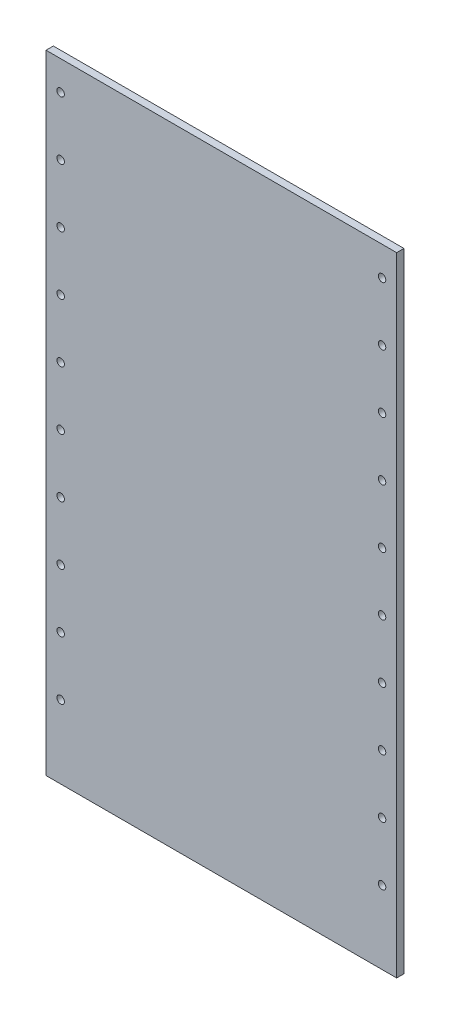
SolidWorks part; units mm, degrees
material "Copper"
ref_plane "Front Plane" through (0, 0, 0) normal (0, 0, 1) x (1, 0, 0)
ref_plane "Top Plane" through (0, 0, 0) normal (0, 1, 0) x (1, 0, 0)
ref_plane "Right Plane" through (0, 0, 0) normal (1, 0, 0) x (0, 0, -1)
sketch "Sketch1" plane through (0, 0, 0) normal (0, 0, 1) x (1, 0, 0)
  line L1 (0, 0) -> (152.4, 0)
  line L2 (0, 0) -> (0, -273.05)
  line L3 (0, -273.05) -> (152.4, -273.05)
  line L4 (152.4, 0) -> (152.4, -273.05)
  circle A0 centre (6.35, -12.7) radius 1.632
  circle A1 centre (146.05, -12.7) radius 1.632
  circle A2 centre (146.05, -38.1) radius 1.632
  circle A3 centre (146.05, -63.5) radius 1.632
  circle A4 centre (146.05, -88.9) radius 1.632
  circle A5 centre (146.05, -114.3) radius 1.632
  circle A6 centre (146.05, -139.7) radius 1.632
  circle A7 centre (146.05, -165.1) radius 1.632
  circle A8 centre (146.05, -190.5) radius 1.632
  circle A9 centre (146.05, -215.9) radius 1.632
  circle A10 centre (146.05, -241.3) radius 1.632
  circle A11 centre (6.35, -38.1) radius 1.6319
  circle A12 centre (6.35, -63.5) radius 1.6319
  circle A13 centre (6.35, -88.9) radius 1.6319
  circle A14 centre (6.35, -114.3) radius 1.6319
  circle A15 centre (6.35, -139.7) radius 1.6319
  circle A16 centre (6.35, -165.1) radius 1.632
  circle A17 centre (6.35, -190.5) radius 1.632
  circle A18 centre (6.35, -215.9) radius 1.632
  circle A19 centre (6.35, -241.3) radius 1.632
  dimension "D3" = 3.2639
  dimension "D1" = 273.05
  dimension "D2" = 152.4
  dimension "D4" = 12.7
  dimension "D5" = 6.35
  dimension "D8" = 6.35
  dimension "D9" = 25.4
  dimension "D6" = 2
  dimension "D7" = 10
extrude "Boss-Extrude1" add sketch "Sketch1" along normal blind 3.175
